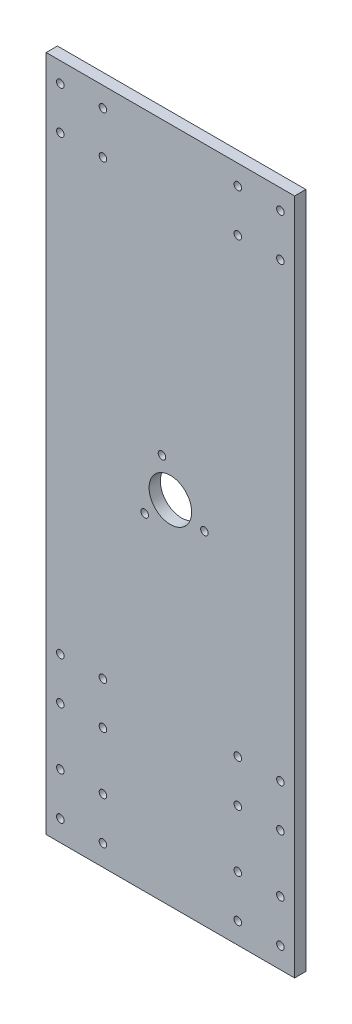
SolidWorks part; units mm, degrees
ref_plane "Front Plane" through (0, 0, 0) normal (0, 0, 1) x (1, 0, 0)
ref_plane "Top Plane" through (0, 0, 0) normal (0, 1, 0) x (1, 0, 0)
ref_plane "Right Plane" through (0, 0, 0) normal (1, 0, 0) x (0, 0, -1)
sketch "Sketch1" plane through (0, 0, 0) normal (0, 0, 1) x (1, 0, 0)
  line L0 (0, 190.825) -> (0, -190.825) construction
  line L1 (-70, -190.825) -> (70, -190.825)
  line L2 (-70, -190.825) -> (-70, 190.825)
  line L3 (-70, 190.825) -> (70, 190.825)
  line L4 (70, -190.825) -> (70, 190.825)
  line L5 (-70, -190.825) -> (70, 190.825) construction
  line L6 (-70, 190.825) -> (70, -190.825) construction
  line L7 (-70, 0) -> (70, 0) construction
  line L8 (-70, 187.65) -> (0, 187.65) construction
  line L9 (-50, 182.9386) -> (-50, 159.7908) construction
  line L12 (-63.1537, 167.65) -> (-35.7543, 167.65) construction
  line L13 (-70, -133.875) -> (74.7966, -133.875) construction
  line L15 (-70, 0.325) -> (70, 0.325) construction
  line L16 (-70, -190.175) -> (70, -190.175) construction
  line L18 (-70, -138.875) -> (70, -138.875) construction
  circle A9 centre (-62, 179.65) radius 2.125
  circle A11 centre (-38, 179.65) radius 2.125
  circle A12 centre (-38, 155.65) radius 2.125
  circle A13 centre (-62, 155.65) radius 2.125
  circle A14 centre (38, 155.65) radius 2.125
  circle A15 centre (62, 155.65) radius 2.125
  circle A16 centre (38, 179.65) radius 2.125
  circle A17 centre (62, 179.65) radius 2.125
  circle A26 centre (62, -179) radius 2.125
  circle A27 centre (38, -179) radius 2.125
  circle A28 centre (62, -155) radius 2.125
  circle A29 centre (38, -155) radius 2.125
  circle A30 centre (-62, -155) radius 2.125
  circle A31 centre (-38, -155) radius 2.125
  circle A32 centre (-38, -179) radius 2.125
  circle A33 centre (-62, -179) radius 2.125
  circle A34 centre (-62, -98.75) radius 2.125
  circle A35 centre (-38, -98.75) radius 2.125
  circle A36 centre (-38, -122.75) radius 2.125
  circle A37 centre (-62, -122.75) radius 2.125
  circle A38 centre (38, -122.75) radius 2.125
  circle A39 centre (62, -122.75) radius 2.125
  circle A40 centre (38, -98.75) radius 2.125
  circle A41 centre (62, -98.75) radius 2.125
  point P0 (0, 0)
  point P72 (74.7966, -135.875)
  dimension "D4" = 4.25
  dimension "D6" = 8
  dimension "D7" = 12
  dimension "D9" = 324.7
  dimension "D11" = 11.175
  dimension "D12" = 5
  dimension "D1" = 381.65
  dimension "D2" = 140
  dimension "D3" = 3.175
  dimension "D5" = 8
  dimension "D8" = 12
  dimension "D10" = 134.2
extrude "Boss-Extrude1" add sketch "Sketch1" along normal blind 6.35
sketch "Sketch2" plane through (0, 0, 6.35) normal (0, 0, 1) x (1, 0, 0)
  line L0 (-70, -207.525) -> (70, -207.525) construction
  line L1 (-70, 190.825) -> (-70, -190.825) construction
  line L2 (70, -190.825) -> (70, 190.825) construction
  line L3 (70, 190.825) -> (-70, 190.825) construction
  line L4 (-70, 7.475) -> (70, 7.475) construction
  circle A0 centre (0, 7.475) radius 12
  circle A1 centre (-4.7306, 26.9075) radius 2.125
  circle A2 centre (19.1943, 1.8556) radius 2.125
  circle A3 centre (-14.4637, -6.3381) radius 2.125
  point P14 (9.4447, -11.3601)
  point P15 (0, 0)
  point P20 (0, 0)
  point P22 (0, 7.475)
  dimension "D3" = 4.25
  dimension "D6" = 24
  dimension "D1" = 398.35
  dimension "D2" = 215
  dimension "D4" = 20
  dimension "D5" = 3
extrude "Cut-Extrude1" cut sketch "Sketch2" against normal through all
